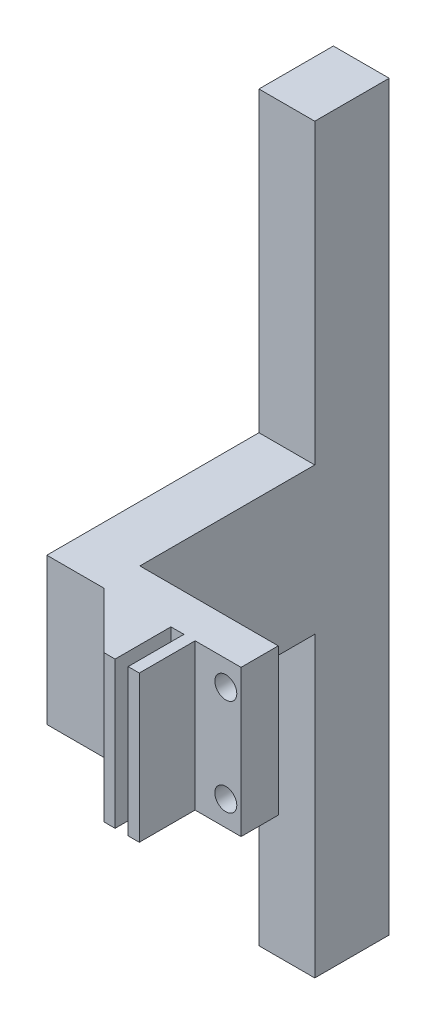
SolidWorks part; units mm, degrees
ref_plane "Front Plane" through (0, 0, 0) normal (0, 0, 1) x (1, 0, 0)
ref_plane "Top Plane" through (0, 0, 0) normal (0, 1, 0) x (1, 0, 0)
ref_plane "Right Plane" through (0, 0, 0) normal (1, 0, 0) x (0, 0, -1)
sketch "Sketch1" plane through (0, 0, 0) normal (0, 0, 1) x (1, 0, 0)
  line L0 (7.0982, 0) -> (17.0982, 0) construction
  line L1 (-17.0982, 0) -> (-7.0982, 0) construction
  line L2 (7.0982, 0) -> (-7.0982, 0) construction
  line L3 (-17.0982, -39.4) -> (-17.0982, 0) construction
  line L4 (7.0982, 0) -> (17.0982, 0)
  line L5 (-17.0982, 0) -> (-7.0982, 0)
  line L6 (7.0982, 0) -> (-7.0982, 0)
  line L7 (-17.0982, -39.4) -> (-17.0982, 0)
  line L8 (17.0982, 0) -> (17.0982, -39.4)
  line L9 (17.0982, -39.4) -> (-17.3138, -39.4)
  circle A0 centre (13, -6.7) radius 2.95 construction
  circle A1 centre (13, -32.7) radius 2.95 construction
  circle A2 centre (-13, -32.7) radius 2.95 construction
  circle A3 centre (-13, -6.7) radius 2.95 construction
  circle A4 centre (13, -6.7) radius 2.95
  circle A5 centre (13, -32.7) radius 2.95
  circle A6 centre (-13, -32.7) radius 2.95
  circle A7 centre (-13, -6.7) radius 2.95
extrude "Boss-Extrude1" add sketch "Sketch1" along normal blind 10 contours L9 L8 L4 L6 L5 L7 A7 A6 A5 A4 region at (0, -19.7, 0)
sketch "Sketch3" plane through (0, 0, 10) normal (0, 0, 1) x (1, 0, 0)
  line L8 (-17.0982, 0) -> (17.0982, 0) construction
  line L9 (1.75, 0) -> (1.75, -39.4)
  line L10 (17.0982, -39.4) -> (-17.0982, -39.4) construction
  line L12 (-1.75, -39.4) -> (-1.75, 0)
  line L14 (1.75, 0) -> (4.75, 0)
  line L15 (4.75, 0) -> (4.75, -39.4)
  line L16 (4.75, -39.4) -> (1.75, -39.4)
  line L17 (-1.75, -39.4) -> (-4.75, -39.4)
  line L18 (-4.75, -39.4) -> (-4.75, 0)
  line L19 (-4.75, 0) -> (-1.75, 0)
extrude "Boss-Extrude2" add sketch "Sketch3" along normal blind 15
sketch "Sketch4" plane through (-17.0982, 0, 0) normal (1, 0, 0) x (0, 0, -1)
  line L1 (0, 0) -> (-10, 0)
  line L2 (0, 0) -> (0, -39.4)
  line L3 (0, -39.4) -> (-10, -39.4)
  line L4 (-10, 0) -> (-10, -39.4)
  dimension "D1" = 39.4
  dimension "D2" = 10
extrude "Boss-Extrude3" add sketch "Sketch4" against normal blind 3
sketch "Sketch5" plane through (0, 0, 10) normal (0, 0, 1) x (1, 0, 0)
  line L1 (-20.0982, -39.4) -> (-35.0982, -39.4)
  line L2 (-20.0982, -39.4) -> (-20.0982, 0)
  line L3 (-20.0982, 0) -> (-35.0982, 0)
  line L4 (-35.0982, -39.4) -> (-35.0982, 0)
  dimension "D1" = 39.4
  dimension "D2" = 15
extrude "Boss-Extrude4" add sketch "Sketch5" against normal blind 77
sketch "Sketch6" plane through (0, 0, 0) normal (0, 1, 0) x (1, 0, 0)
  line L1 (-20.0982, 67) -> (-35.0982, 67)
  line L2 (-20.0982, 67) -> (-20.0982, 47)
  line L3 (-20.0982, 47) -> (-35.0982, 47)
  line L4 (-35.0982, 67) -> (-35.0982, 47)
  line L5 (-35.0982, 67) -> (-35.0982, -10) construction
  dimension "D1" = 20
  dimension "D2" = 15
extrude "Boss-Extrude5" add sketch "Sketch6" along normal blind 80
sketch "Sketch7" plane through (0, -39.4, 0) normal (0, -1, 0) x (-1, 0, 0)
  line L0 (35.0982, 47) -> (20.0982, 47) construction
  line L1 (35.0982, 47) -> (20.0982, 47)
  line L2 (35.0982, 47) -> (35.0982, 67)
  line L3 (35.0982, 67) -> (20.0982, 67)
  line L4 (20.0982, 67) -> (20.0982, 47)
extrude "Boss-Extrude6" add sketch "Sketch7" along normal blind 80
chamfer "Chamfer1" distance 15 angle 45 1 edges at (-4.75, -19.7, 10)
sketch "Sketch8" plane through (0, 0, 10) normal (0, 0, 1) x (1, 0, 0)
  circle A0 centre (-13, -32.7) radius 5
  circle A1 centre (-13, -6.7) radius 5
